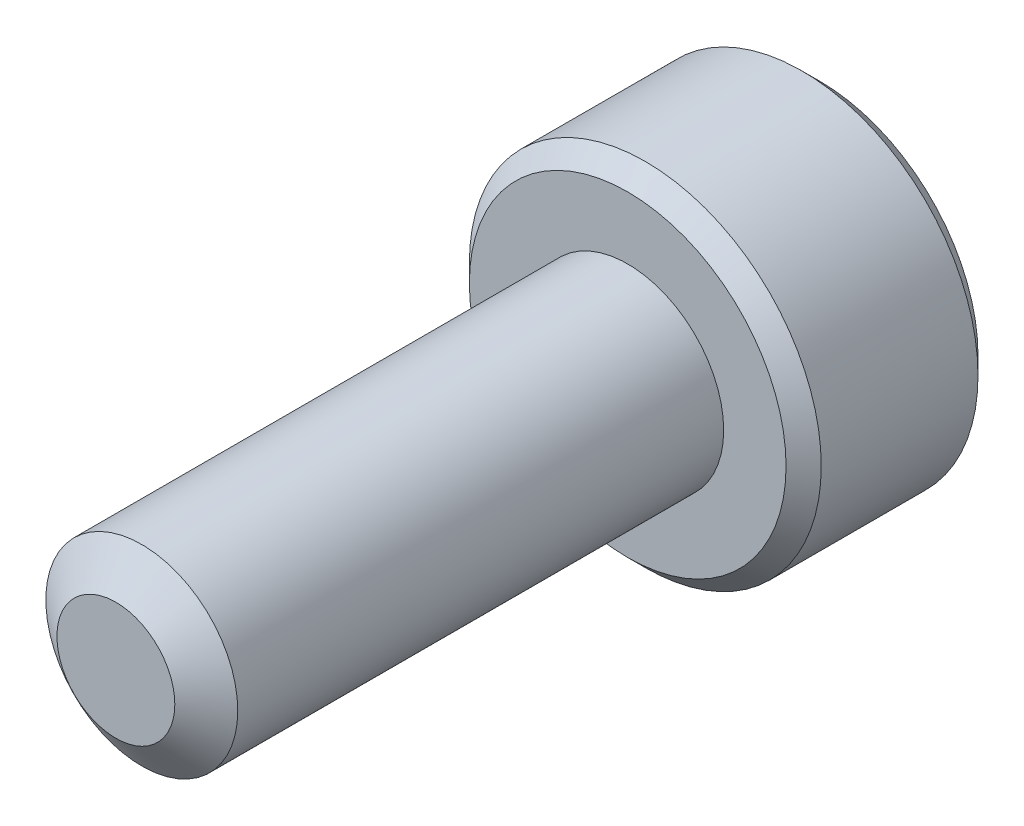
SolidWorks part; units mm, degrees
other "DetailItem1"
material "1.4310 (X10CrNi18-8)"
ref_plane "Front Plane" through (0, 0, 0) normal (0, 0, 1) x (1, 0, 0)
ref_plane "Top Plane" through (0, 0, 0) normal (0, 1, 0) x (1, 0, 0)
ref_plane "Right Plane" through (0, 0, 0) normal (1, 0, 0) x (0, 0, -1)
sketch "Sketch1" plane through (0, 0, 0) normal (0, 0, 1) x (1, 0, 0)
  circle A0 centre (0, 0) radius 1.5
  dimension "OD" = 3
extrude "Extrude1" add sketch "Sketch1" against normal blind 8
sketch "Sketch2" plane through (0, 0, 0) normal (0, 0, 1) x (1, 0, 0)
  circle A0 centre (0, 0) radius 1.5 construction
  circle A1 centre (0, 0) radius 1.5
curve "Helix/Spiral1" pitch 0.5 height 8.5 turns 17 parameters "pitch"=0.5
sketch "Sketch3" plane through (0, 0, 0) normal (1, 0, 0) x (0, 0, -1)
  line L0 (-0.4375, 1.5) -> (-0.25, 1.1752)
  line L1 (-0.25, 1.1752) -> (-0.1875, 1.1752)
  line L2 (-0.1875, 1.1752) -> (0, 1.5)
  line L3 (-0.4375, 1.5) -> (0, 1.5)
  line L4 (-0.2187, 1.5) -> (-0.2188, 1.1752) construction
  line L5 (-0.3438, 1.3376) -> (-0.0938, 1.3376) construction
  line L6 (0, 1.5) -> (0, -1.5) construction
  dimension "D1" = 0.0625
  dimension "D2" = 0.25
  dimension "D3" = 60
sweep "Cut-Sweep1" [suppressed] cut profiles "Sketch3" path "Helix/Spiral1"
sketch "Sketch4" plane through (0, 0, 0) normal (1, 0, 0) x (0, 0, -1)
  line L0 (0.4053, 1.5) -> (0, 0.9212)
  line L1 (0, 0.9212) -> (0, 1.5)
  line L2 (0.4053, 1.5) -> (0, 1.5)
  line L3 (-0.4375, 1.5) -> (0, 1.5) construction
  line L4 (0, 0) -> (7.0209, 0) construction
  dimension "D1" = 55
  dimension "D2" = 0.254
revolve "Cut-Revolve1" cut sketch "Sketch4" angle 360 about L4
sketch "Sketch6" plane through (0, 0, -8) normal (0, 0, -1) x (-1, 0, 0)
  circle A0 centre (0, 0) radius 2.75
  dimension "head dia" = 5.5
extrude "Extrude2" add sketch "Sketch6" along normal blind 3
sketch "Sketch7" plane through (0, 0, -11) normal (0, 0, -1) x (-1, 0, 0)
  line L1 (0, 1.4434) -> (-1.25, 0.7217)
  line L2 (-1.25, 0.7217) -> (-1.25, -0.7217)
  line L3 (-1.25, -0.7217) -> (0, -1.4434)
  line L4 (0, -1.4434) -> (1.25, -0.7217)
  line L5 (1.25, -0.7217) -> (1.25, 0.7217)
  line L6 (1.25, 0.7217) -> (0, 1.4434)
  circle A0 centre (0, 0) radius 1.25 construction
  dimension "hex dia" = 2.5
extrude "Cut-Extrude1" cut sketch "Sketch7" against normal blind 1.875
sketch "Sketch8" plane through (0, 0, -11) normal (0, 0, -1) x (-1, 0, 0)
  circle A0 centre (0, 0) radius 1.4434
extrude "Cut-Extrude2" cut sketch "Sketch8" against normal through all draft 45
chamfer "Chamfer1" distance 0.275 angle 45 2 edges at (-2.75, 0, -11) (-2.75, 0, -8)
sketch "Sketch10" plane through (0, 0, -8) normal (0, 0, 1) x (1, 0, 0)
  circle A1 centre (0, 0) radius 1.5
  circle A2 centre (0, 0) radius 1.5
  dimension "D1" = 0
ref_plane "Plane1" through (0, 0, 0) normal (0, 0, 1) x (1, 0, 0)
extrude "partial thread" [suppressed] add sketch "Sketch10" along normal up to surface (4 mm away) separate body up to plane "Plane1"
chamfer "Chamfer2" [suppressed] distance 0.06 angle 45
combine bodies "Combine1" [suppressed] operation type add bodies to combine 107 108
sketch "Sketch9" plane through (0, 0, 0) normal (1, 0, 0) x (0, 0, -1)
  line L0 (0, 1.5) -> (0, -1.5) construction
  line L1 (1.25, 1.5) -> (1.25, -1.5) construction
  dimension "D1" = 1.25
equation "\"D3@Helix/Spiral1\" = \"screw length@Extrude1\"+\"pitch@Helix/Spiral1\""
equation "\"D1@Sketch3\" = \"pitch@Helix/Spiral1\"*.125"
equation "\"D2@Sketch3\" = \"pitch@Helix/Spiral1\"*.5"
equation "\"D1@Cut-Extrude1\" = \"hex dia@Sketch7\"*.75"
equation "\"D1@Chamfer1\" = \"head dia@Sketch6\"*.05"
equation "\"D1@Sketch9\" = \"pitch@Helix/Spiral1\"*2.5"
equation "\"D1@Chamfer2\"=\"OD@Sketch1\"*.02"
